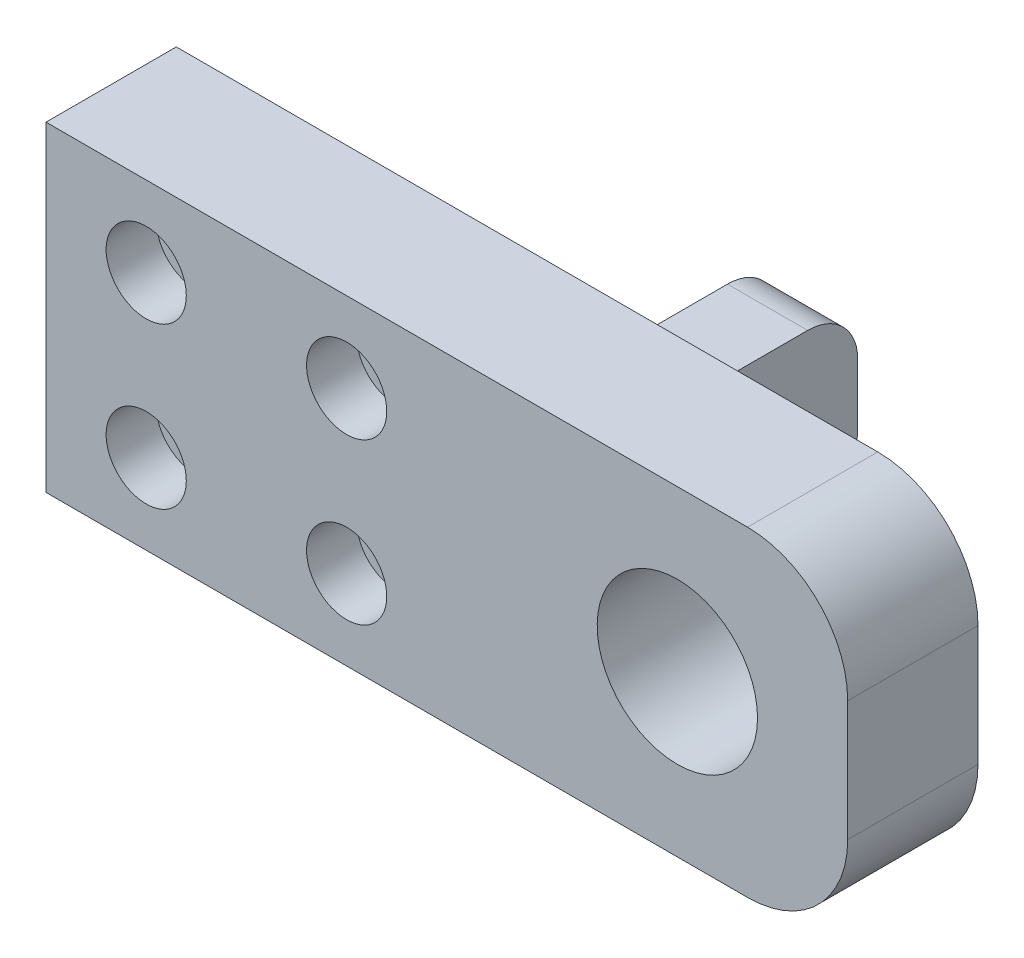
SolidWorks part; units mm, degrees
ref_plane "Alzado" through (0, 0, 0) normal (0, 0, 1) x (1, 0, 0)
ref_plane "Planta" through (0, 0, 0) normal (0, 1, 0) x (1, 0, 0)
ref_plane "Vista lateral" through (0, 0, 0) normal (1, 0, 0) x (0, 0, -1)
sketch "Croquis1" plane through (0, 0, 0) normal (0, 0, 1) x (1, 0, 0)
  line L0 (-10, -240) -> (-10, 0) construction
  line L1 (-10, -68) -> (70, -68)
  line L2 (-10, -68) -> (-10, -36)
  line L3 (-10, -36) -> (70, -36)
  line L4 (70, -68) -> (70, -36)
  line L5 (53, -52) -> (70, -52) construction
  circle A0 centre (53, -52) radius 8
  dimension "D1" = 16
  dimension "D2" = 32
  dimension "D3" = 80
extrude "Saliente-Extruir1" add sketch "Croquis1" along normal blind 13
sketch "Croquis2" plane through (0, 0, 13) normal (0, 0, 1) x (1, 0, 0)
  line L0 (-10, -52) -> (70, -52) construction
  line L1 (-10, -36) -> (-10, -68) construction
  line L2 (70, -68) -> (70, -36) construction
  circle A0 centre (0, -44) radius 2.05
  circle A1 centre (20, -44) radius 2.05
  circle A2 centre (0, -60) radius 2.05
  circle A3 centre (20, -60) radius 2.05
  dimension "D1" = 4.1
  dimension "D2" = 10
  dimension "D3" = 20
  dimension "D4" = 16
extrude "Cortar-Extruir1" cut sketch "Croquis2" against normal up to next
sketch "Croquis3" plane through (0, 0, 13) normal (0, 0, 1) x (1, 0, 0)
  circle A0 centre (0, -44) radius 4
  circle A1 centre (20, -44) radius 4
  circle A2 centre (20, -60) radius 4
  circle A3 centre (0, -60) radius 4
  dimension "D1" = 8
extrude "Cortar-Extruir2" cut sketch "Croquis3" against normal blind 5
fillet "Redondeo1" radius 10 2 edges at (70, -68, 6.5) (70, -36, 6.5)
sketch "Croquis4" plane through (0, 0, 0) normal (0, 0, -1) x (-1, 0, 0)
  line L0 (-30, -44) -> (-30, -60) construction
  line L3 (10, -36) -> (10, -68) construction
  line L4 (10, -68) -> (-60, -68) construction
  line L5 (-30, -44) -> (-38, -44)
  line L6 (-30, -44) -> (-30, -60)
  line L7 (-30, -60) -> (-38, -60)
  line L8 (-38, -44) -> (-38, -60)
  line L9 (-60, -36) -> (10, -36) construction
  dimension "D1" = 40
  dimension "D2" = 8
  dimension "D3" = 8
  dimension "D4" = 8
extrude "Saliente-Extruir2" add sketch "Croquis4" along normal blind 20
sketch "Croquis5" plane through (38, 0, 0) normal (1, 0, 0) x (0, 0, -1)
  line L0 (10, -44) -> (10, -60) construction
  line L1 (20, -44) -> (0, -44) construction
  line L2 (20, -60) -> (0, -60) construction
  circle A0 centre (10, -52) radius 2.05
  dimension "D1" = 4.1
extrude "Cortar-Extruir3" cut sketch "Croquis5" against normal up to next
sketch "Croquis6" plane through (38, 0, 0) normal (1, 0, 0) x (0, 0, -1)
  circle A0 centre (10, -52) radius 4
  dimension "D1" = 8
extrude "Cortar-Extruir4" cut sketch "Croquis6" against normal blind 3
fillet "Redondeo2" radius 8 3 edges at (34, -44, 0) (34, -60, 0) (38, -52, 0)
fillet "Redondeo3" radius 5 2 edges at (34, -44, -20) (34, -60, -20)
